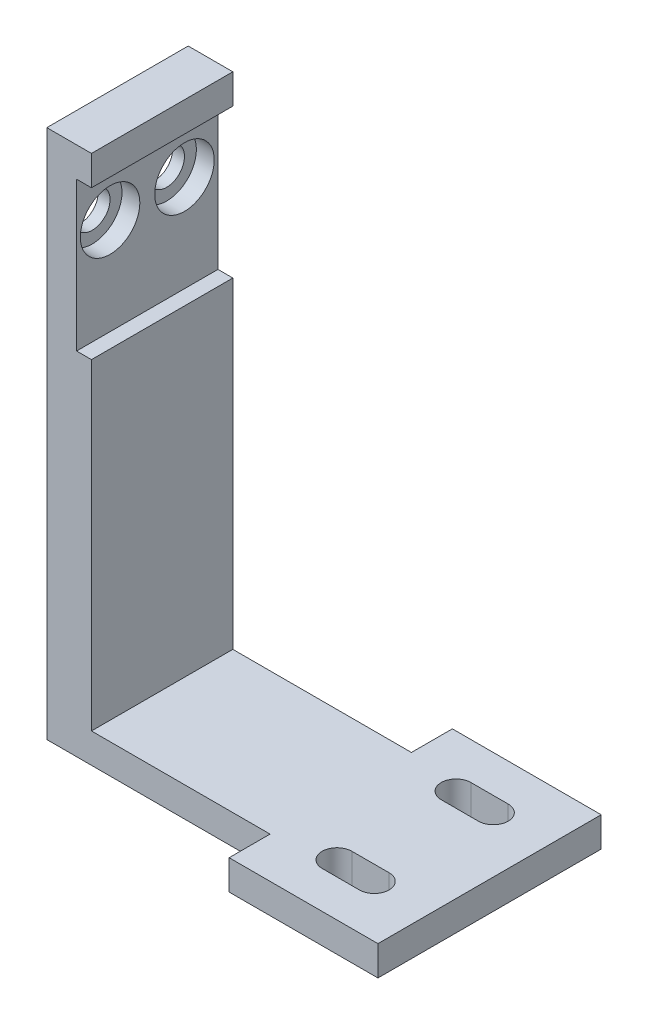
SolidWorks part; units mm, degrees
material "6061-T6 (SS)"
ref_plane "Front Plane" through (0, 0, 0) normal (0, 0, 1) x (1, 0, 0)
ref_plane "Top Plane" through (0, 0, 0) normal (0, 1, 0) x (1, 0, 0)
ref_plane "Right Plane" through (0, 0, 0) normal (1, 0, 0) x (0, 0, -1)
sketch "Sketch1" plane through (0, 0, 0) normal (0, 0, 1) x (1, 0, 0)
  line L0 (-15.4886, 20.5) -> (-17.5374, 20.5) construction
  line L9 (-17.5374, 15.5) -> (-17.5374, 25.5)
  line L10 (-19.5374, 0) -> (-19.5374, 27.5)
  line L11 (-19.5374, 27.5) -> (-16.5374, 27.5)
  line L12 (-16.5374, 27.5) -> (-16.5374, 25.5)
  line L17 (-10.4274, -6.11) -> (5.4626, -6.11)
  line L18 (5.4626, -6.11) -> (5.4626, -8.11)
  line L19 (5.4626, -8.11) -> (-11.4274, -8.11)
  line L20 (-17.5374, 25.5) -> (-16.5374, 25.5)
  line L21 (-17.5374, 15.5) -> (-16.5374, 15.5)
  line L22 (-16.5374, 15.5) -> (-16.5374, 12.5)
  line L23 (-19.5374, 0) -> (-19.5374, -8.11)
  line L24 (-19.5374, -8.11) -> (-11.4274, -8.11)
  line L25 (-16.5374, 12.5) -> (-16.5374, -6.11)
  line L26 (-16.5374, -6.11) -> (-10.4274, -6.11)
  line L29 (-10.4274, -6.11) -> (-8.0144, -6.11) construction
  point P15 (-17.5374, 20.5)
  point P21 (-12.4274, 0)
  dimension "D3" = 35.61
  dimension "D4" = 3
  dimension "D2" = 3
  dimension "D5" = 25
  dimension "D6" = 10
  dimension "D7" = 2
  dimension "D8" = 1
  dimension "D10" = 2
extrude "Boss-Extrude1" add sketch "Sketch1" along normal mid plane 9.5
sketch "Sketch2" plane through (-17.5374, 0, 0) normal (1, 0, 0) x (0, 0, -1)
  line L0 (-4.75, 20.5) -> (4.75, 20.5) construction
  line L1 (-4.75, 15.5) -> (-4.75, 25.5) construction
  line L2 (4.75, 15.5) -> (4.75, 25.5) construction
  line L3 (-4.75, 22) -> (4.75, 22) construction
  line L4 (0, 22) -> (0, 20.5) construction
  point P8 (-2.5, 22)
  point P11 (2.5, 22)
  dimension "D2" = 2.5
  dimension "D1" = 1.5
hole_wizard "M2 Clearance Hole1" positions "3DSketch1" profile "Sketch3" hole size "M2" standard "ANSI Metric" end condition through all
sketch3d "3DSketch1"
  point P0 (-17.5374, 22, 2.5)
  point P3 (-17.5374, 22, -2.5)
sketch "Sketch3" plane through (-17.5374, 22, 2.5) normal (0, 1, 0) x (0, 0, -1)
  line L0 (0, 0) -> (0, 2)
  line L1 (0, 2) -> (1.2, 2)
  line L2 (1.2, 2) -> (1.2, 0)
  line L5 (1.2, 0) -> (0, 0)
  line L11 (0, -6.35) -> (0, 107.95) construction
  dimension "Thru Hole Dia." = 2.4
  dimension "Thru Hole Depth" = 2
sketch "Sketch4" plane through (-17.5374, 0, 0) normal (1, 0, 0) x (0, 0, -1)
  circle A0 centre (-2.5, 22) radius 2
  circle A1 centre (2.5, 22) radius 2
  dimension "D1" = 4
  dimension "D2" = 4
extrude "Cut-Extrude1" cut sketch "Sketch4" against normal blind 1.2
sketch "Sketch5" plane through (0, -8.11, 0) normal (0, -1, 0) x (1, 0, 0)
  line L0 (5.4626, -7.5) -> (5.4626, 7.5)
  line L1 (5.4626, 4.75) -> (5.4626, -4.75) construction
  line L2 (5.4626, 7.5) -> (-4.5374, 7.5)
  line L3 (-4.5374, 7.5) -> (-4.5374, -7.5)
  line L4 (-4.5374, -7.5) -> (5.4626, -7.5)
  point P3 (5.4626, 0)
  dimension "D1" = 10
  dimension "D2" = 15
extrude "Boss-Extrude2" add sketch "Sketch5" against normal blind 2
sketch "Sketch6" plane through (0, -6.11, 0) normal (0, 1, 0) x (1, 0, 0)
  line L0 (5.4626, 0) -> (-4.5374, 0) construction
  line L1 (5.4626, 7.5) -> (5.4626, -7.5) construction
  line L2 (1.7126, -4) -> (-0.7874, -4) construction
  line L3 (0.4626, -7.5) -> (0.4626, 7.5) construction
  line L4 (5.4626, -7.5) -> (-4.5374, -7.5) construction
  line L5 (-4.5374, 7.5) -> (5.4626, 7.5) construction
  line L6 (1.7126, -5) -> (-0.7874, -5)
  line L7 (1.7126, -3) -> (-0.7874, -3)
  line L8 (1.7126, 4) -> (-0.7874, 4) construction
  line L9 (1.7126, 5) -> (-0.7874, 5)
  line L10 (1.7126, 3) -> (-0.7874, 3)
  arc A0 (1.7126, -5) -> (1.7126, -3) centre (1.7126, -4) ccw
  arc A1 (-0.7874, -3) -> (-0.7874, -5) centre (-0.7874, -4) ccw
  arc A2 (1.7126, 5) -> (1.7126, 3) centre (1.7126, 4) cw
  arc A3 (-0.7874, 3) -> (-0.7874, 5) centre (-0.7874, 4) cw
  point P12 (0.4626, -4)
  point P13 (0.4626, 0)
  point P14 (0.4626, 4)
  point P15 (0.4626, -4)
  point P23 (0.4626, 4)
  dimension "D3" = 1
  dimension "D1" = 4
  dimension "D2" = 2.5
extrude "Cut-Extrude2" cut sketch "Sketch6" against normal up to surface (2 mm away) up to face at (-5.7874, -8.11, 0)
